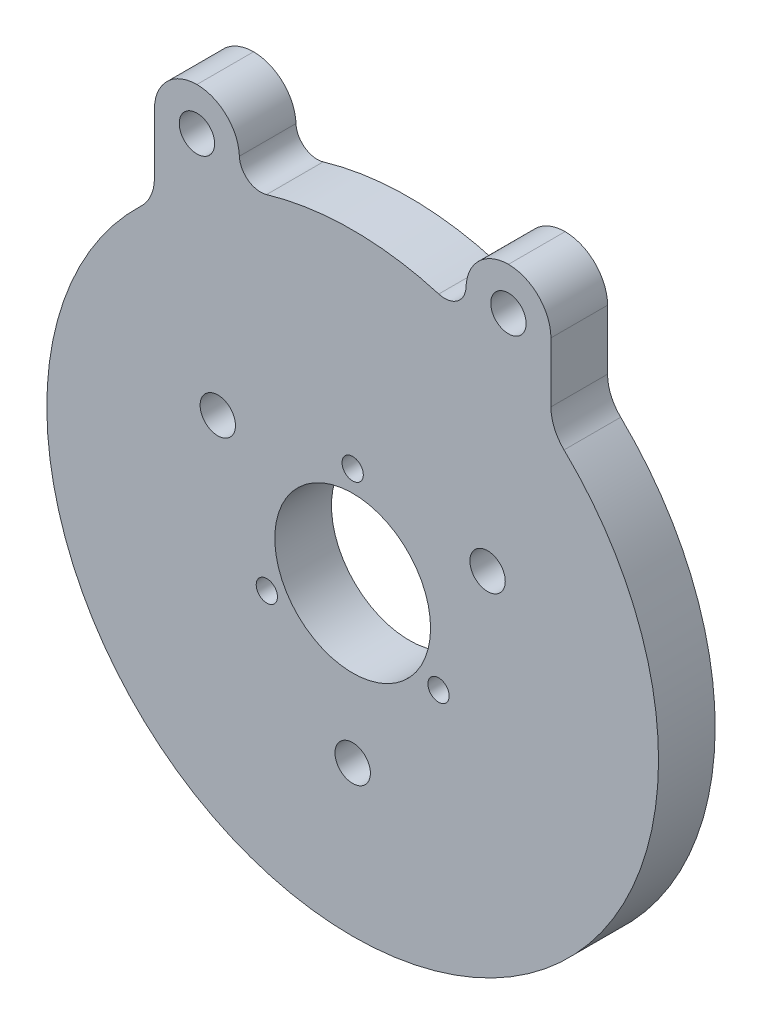
SolidWorks part; units mm, degrees
note: '?' marks a value the reader was unsure of.
ref_plane "Front" through (0, 0, 0) normal (0, 0, 1) x (1, 0, 0)
ref_plane "Top" through (0, 0, 0) normal (0, 1, 0) x (1, 0, 0)
ref_plane "Right" through (0, 0, 0) normal (1, 0, 0) x (0, 0, -1)
sketch "Sketch1" plane through (0, 0, 0) normal (0, 0, 1) x (1, 0, 0)
  circle A0 centre (0, 0) radius 21.6
  dimension "D1" = 43.2
extrude "Extrude1" add sketch "Sketch1" along normal blind 4
sketch "Sketch2" plane through (0, 0, 4) normal (0, 0, 1) x (1, 0, 0)
  line L0 (-14, 16.4487) -> (-14, 25)
  line L1 (-14, 25) -> (-8, 25)
  line L2 (14, 25) -> (14, 16.4487)
  line L3 (-8, 25) -> (-8, 20.0639)
  line L4 (14, 25) -> (8, 25)
  line L5 (8, 25) -> (8, 20.0639)
  circle A0 centre (0, 0) radius 21.6 construction
  arc A1 (-14, 16.4487) -> (14, 16.4487) centre (0, 0) cw
  circle A2 centre (-11, 22) radius 1.25
  circle A3 centre (11, 22) radius 1.25
  circle M1 centre (0, 0) radius 21.6
  dimension "D1" = 21.6
  dimension "D7" = 2.5
  dimension "D8" = 2.5
  dimension "D2" = 14
  dimension "D3" = 14
  dimension "D4" = 6
  dimension "D5" = 6
  dimension "D6" = 25
  dimension "D9" = 3
  dimension "D10" = 3
  dimension "D11" = 3
extrude "Extrude2" add sketch "Sketch2" against normal up to surface (4 mm away) contours L4 L5 L2 A3 M1 | L3 L1 L0 A2 M1 up to face at (21.6, 0, 0)
fillet "Fillet1" radius 3 6 edges at (14, 16.4487, 2) (-14, 16.4487, 2) (14, 25, 2) (8, 25, 2) (-8, 25, 2) (-14, 25, 2)
fillet "Fillet2" radius 1.5 2 edges at (8, 20.0639, 2) (-8, 20.0639, 2)
sketch "Sketch3" plane through (0, 0, 4) normal (0, 0, 1) x (1, 0, 0)
  circle A0 centre (0, 0) radius 5.5
  dimension "D1" = 11
extrude "Extrude3" cut sketch "Sketch3" against normal up to surface (4 mm away) up to face at (0, 17.6204, 0)
sketch "Sketch4" plane through (0, 0, 4) normal (0, 0, 1) x (1, 0, 0)
  circle A0 centre (0, 7) radius 0.75
  dimension "D1" = 1.5
  dimension "D2" = 7
ref_axis "Axis1" through (0, 0, 0) along (0, 0, 1)?
extrude "Extrude4" cut sketch "Sketch4" against normal up to surface (4 mm away) up to face at (5.5, 0, 0)
pattern_circular "CirPattern1" count 3 over 360 about axis through (0, 0, 0) along (0, 0, 1) of "Extrude4"
sketch "Sketch5" plane through (0, 0, 4) normal (0, 0, 1) x (1, 0, 0)
  circle A0 centre (0, -11) radius 1.25
  dimension "D1" = 2.5
  dimension "D2" = 11
extrude "Extrude5" cut sketch "Sketch5" against normal up to surface (4 mm away) up to face at (6.8122, -3.5, 0)
pattern_circular "CirPattern2" count 3 over 360 about axis through (0, 0, 0) along (0, 0, 1) of "Extrude5"
